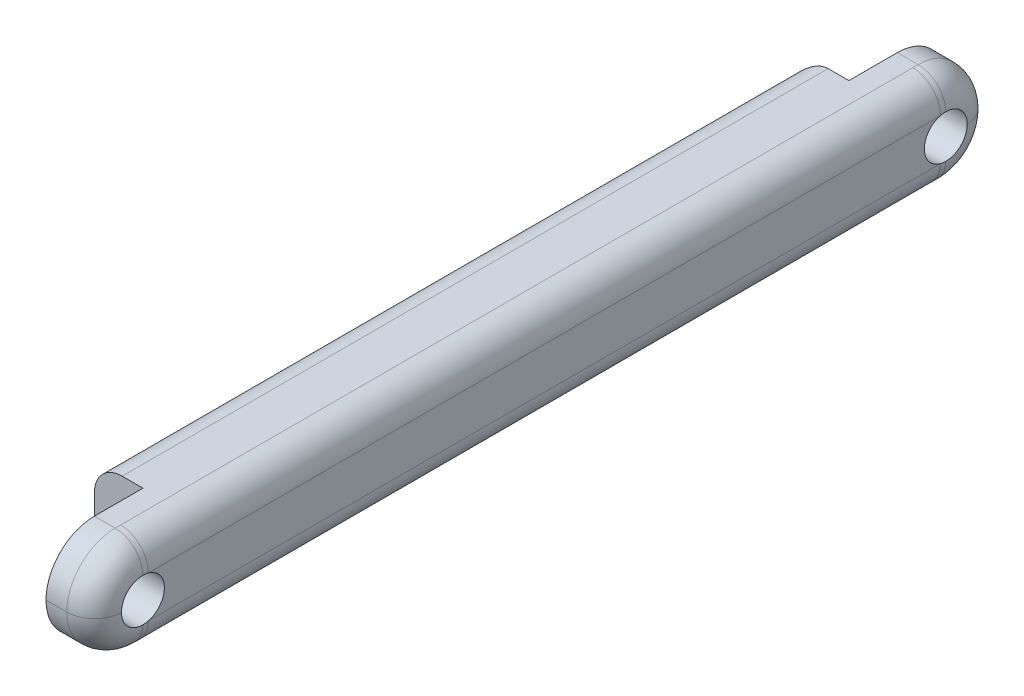
SolidWorks part; units mm, degrees
ref_plane "前视基准面" through (0, 0, 0) normal (0, 0, 1) x (1, 0, 0)
ref_plane "上视基准面" through (0, 0, 0) normal (0, 1, 0) x (1, 0, 0)
ref_plane "右视基准面" through (0, 0, 0) normal (1, 0, 0) x (0, 0, -1)
sketch "草图1" plane through (0, 0, 0) normal (0, 0, 1) x (1, 0, 0)
  line L1 (-3.5, 3.5) -> (3.5, 3.5)
  line L2 (-3.5, 3.5) -> (-3.5, -3.5)
  line L3 (-3.5, -3.5) -> (3.5, -3.5)
  line L4 (3.5, 3.5) -> (3.5, -3.5)
  line L5 (-3.5, 3.5) -> (3.5, -3.5) construction
  line L6 (-3.5, -3.5) -> (3.5, 3.5) construction
  point P0 (0, 0)
  dimension "D1" = 7
  dimension "D2" = 7
extrude "凸台-拉伸1" add sketch "草图1" along normal blind 51
sketch "草图2" plane through (0, 0, 51) normal (0, 0, 1) x (1, 0, 0)
  line L0 (3.5, 3.5) -> (-3.5, 3.5) construction
  line L1 (0, 3.5) -> (3.5, 3.5)
  line L2 (0, 3.5) -> (0, -3.5)
  line L3 (0, -3.5) -> (3.5, -3.5)
  line L4 (3.5, 3.5) -> (3.5, -3.5)
extrude "凸台-拉伸2" add sketch "草图2" along normal blind 7
sketch "草图3" plane through (0, 0, 0) normal (0, 0, -1) x (-1, 0, 0)
  line L0 (3.5, -3.5) -> (-3.5, -3.5) construction
  line L1 (0, -3.5) -> (-3.5, -3.5)
  line L2 (0, -3.5) -> (0, 3.5)
  line L3 (0, 3.5) -> (-3.5, 3.5)
  line L4 (-3.5, -3.5) -> (-3.5, 3.5)
extrude "凸台-拉伸3" add sketch "草图3" along normal blind 7
fillet "圆角1" radius 3.5 4 edges at (1.75, -3.5, 58) (1.75, 3.5, 58) (1.75, 3.5, -7) (1.75, -3.5, -7)
sketch "草图4" plane through (0, 0, 0) normal (-1, 0, 0) x (0, 0, 1)
  circle A0 centre (54.5, 0) radius 1.55
  circle A1 centre (-3.5, 0) radius 1.55
  dimension "D1" = 3.1
  dimension "D2" = 3.1
extrude "切除-拉伸1" cut sketch "草图4" against normal blind 3.5
sketch "草图5" plane through (-3.5, 0, 0) normal (-1, 0, 0) x (0, 0, 1)
  line L0 (0, 3.5) -> (7, -3.5)
  line L1 (51, -3.5) -> (0, -3.5) construction
  line L2 (7, -3.5) -> (0, -3.5)
  line L3 (0, -3.5) -> (0, 3.5)
extrude "切除-拉伸2" cut sketch "草图5" against normal blind 3.5
fillet "圆角2" radius 2 4 edges at (3.5, -3.5, 25.5) (-3.5, -3.5, 29) (3.5, 3.5, 25.5) (-3.5, 3.5, 25.5)
